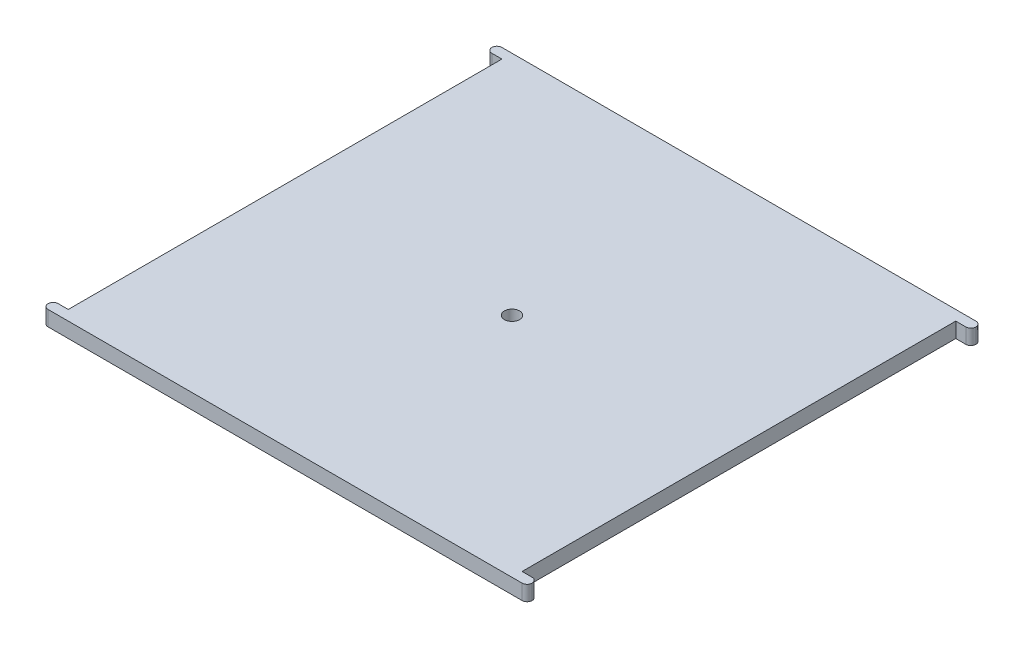
SolidWorks part; units mm, degrees
ref_plane "Front Plane" through (0, 0, 0) normal (0, 0, 1) x (1, 0, 0)
ref_plane "Top Plane" through (0, 0, 0) normal (0, 1, 0) x (1, 0, 0)
ref_plane "Right Plane" through (0, 0, 0) normal (1, 0, 0) x (0, 0, -1)
sketch "Sketch1" plane through (0, 0, 0) normal (0, 1, 0) x (1, 0, 0)
  line L0 (-71.4375, 65.0875) -> (71.4375, 65.0875) construction
  line L1 (-71.4375, -71.4375) -> (71.4375, -71.4375)
  line L2 (-71.4375, -68.2625) -> (-71.4375, 68.2625)
  line L3 (-71.4375, 71.4375) -> (71.4375, 71.4375)
  line L4 (71.4375, -68.2625) -> (71.4375, 68.2625)
  line L5 (-71.4375, -71.4375) -> (71.4375, 71.4375) construction
  line L6 (-71.4375, 71.4375) -> (71.4375, -71.4375) construction
  line L7 (-71.4375, 68.2625) -> (71.4375, 68.2625) construction
  line L8 (-71.4375, -68.2625) -> (71.4375, -68.2625) construction
  line L9 (-71.4375, 71.4375) -> (-76.2, 71.4375)
  line L11 (-71.4375, 68.2625) -> (-76.2, 68.2625)
  line L12 (-76.2, 71.4375) -> (-76.2, 68.2625)
  line L13 (71.4375, 71.4375) -> (76.2, 71.4375)
  line L14 (-71.4375, -68.2625) -> (-76.2, -68.2625)
  line L15 (71.4375, 68.2625) -> (76.2, 68.2625)
  line L16 (76.2, 71.4375) -> (76.2, 68.2625)
  line L18 (-71.4375, -71.4375) -> (-76.2, -71.4375)
  line L19 (-76.2, -68.2625) -> (-76.2, -71.4375)
  line L20 (71.4375, -68.2625) -> (76.2, -68.2625)
  line L22 (71.4375, -71.4375) -> (76.2, -71.4375)
  line L23 (76.2, -68.2625) -> (76.2, -71.4375)
  point P0 (0, 0)
  dimension "D1" = 142.875
  dimension "D2" = 6.35
  dimension "D3" = 3.175
  dimension "D4" = 4.7625
  dimension "D5" = 4.7625
  dimension "D6" = 3.175
  dimension "D7" = 4.7625
  dimension "D8" = 4.7625
extrude "Boss-Extrude1" add sketch "Sketch1" along normal blind 4.7625
hole_wizard "3/16 (0.1875) Diameter Hole1" positions "Sketch2" profile "Sketch3" hole size "3/16" standard "ANSI Inch" end condition through all
sketch "Sketch2" plane through (0, 4.7625, 0) normal (0, 1, 0) x (1, 0, 0)
  line L7 (-76.2, 71.4375) -> (76.2, -71.4375) construction
  point P44 (0, 0)
sketch "Sketch3" plane through (0, 4.7625, 0) normal (1, 0, 0) x (0, 0, 1)
  line L0 (0, 0) -> (0, 4.7625)
  line L1 (0, 4.7625) -> (2.3812, 4.7625)
  line L2 (2.3812, 4.7625) -> (2.3812, 0)
  line L5 (2.3812, 0) -> (0, 0)
  line L11 (0, -6.35) -> (0, 107.95) construction
  dimension "Thru Hole Dia." = 4.7625
  dimension "Thru Hole Depth" = 4.7625
fillet "Fillet1" radius 1.5875 8 edges at (-76.2, 2.3813, 71.4375) (-76.2, 2.3813, 68.2625) (76.2, 2.3813, 71.4375) (76.2, 2.3813, 68.2625) (76.2, 2.3813, -68.2625) (76.2, 2.3813, -71.4375) (-76.2, 2.3813, -68.2625) (-76.2, 2.3813, -71.4375)
